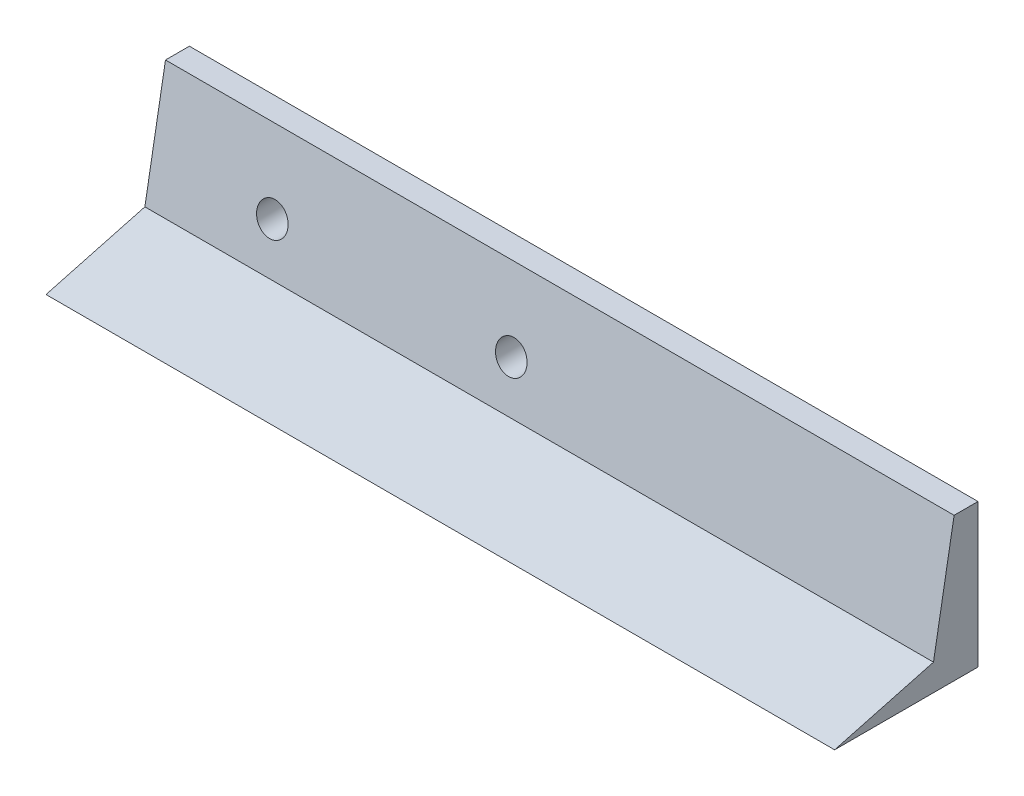
SolidWorks part; units mm, degrees
ref_plane "Front Plane" through (0, 0, 0) normal (0, 0, 1) x (1, 0, 0)
ref_plane "Top Plane" through (0, 0, 0) normal (0, 1, 0) x (1, 0, 0)
ref_plane "Right Plane" through (0, 0, 0) normal (1, 0, 0) x (0, 0, -1)
sketch "Sketch1" plane through (0, 0, 0) normal (1, 0, 0) x (0, 0, -1)
  line L0 (0, 0) -> (0, 30)
  line L3 (-30, 0) -> (0, 0)
  line L4 (-30, 0) -> (-9.3124, 5.5432)
  line L5 (-9.3124, 5.5432) -> (-5, 30)
  line L6 (-5, 30) -> (0, 30)
  dimension "D1" = 30
  dimension "D2" = 30
  dimension "D3" = 10
  dimension "D4" = 15
  dimension "D5" = 5
extrude "Boss-Extrude1" add sketch "Sketch1" along normal blind 100
sketch "Sketch2" plane through (0, 0, 0) normal (0, 0, -1) x (-1, 0, 0)
  line L0 (-100, 15) -> (0, 15) construction
  line L1 (-100, 0) -> (-100, 30) construction
  line L2 (0, 0) -> (0, 30) construction
  line L3 (-100, 30) -> (0, 30) construction
  point P8 (-75, 15)
  point P9 (-25, 15)
  dimension "D1" = 15
  dimension "D2" = 25
  dimension "D3" = 25
hole_wizard "M3 Clearance Hole1" positions "Sketch2" profile "Sketch3" hole size "M3" standard "ANSI Metric" end condition through all
sketch "Sketch3" plane through (25, 15, 0) normal (1, 0, 0) x (0, 1, 0)
  line L0 (0, 0) -> (0, 30)
  line L1 (0, 30) -> (1.7, 30)
  line L2 (1.7, 30) -> (1.7, 0)
  line L5 (1.7, 0) -> (0, 0)
  line L11 (0, -6.35) -> (0, 107.95) construction
  dimension "Thru Hole Dia." = 3.4
  dimension "Thru Hole Depth" = 30
ref_plane "Plane1" through (0, 0, 2.5) normal (0, 0, -1) x (-1, 0, 0)
sketch "Sketch4" plane through (0, 0, 2.5) normal (0, 0, -1) x (-1, 0, 0)
  circle A0 centre (-75, 15) radius 3.25
  circle A1 centre (-25, 15) radius 3.25
  dimension "D1" = 6.5
extrude "Cut-Extrude1" cut sketch "Sketch4" against normal through all
sketch "Sketch6" plane through (100, 0, 0) normal (-1, 0, 0) x (0, 0, 1)
  line L5 (0, 0) -> (30, 0)
  line L6 (30, 0) -> (9.3124, 5.5432)
  line L7 (9.3124, 5.5432) -> (5, 30)
  line L8 (5, 30) -> (0, 30)
  line L9 (0, 30) -> (0, 0)
  line L10 (0, 0) -> (30, 0)
  line L11 (30, 0) -> (9.3124, 5.5432)
  line L12 (9.3124, 5.5432) -> (5, 30)
  line L13 (5, 30) -> (0, 30)
  line L14 (0, 30) -> (0, 0)
  dimension "D1" = 0
extrude "Boss-Extrude2" add sketch "Sketch6" against normal blind 65
